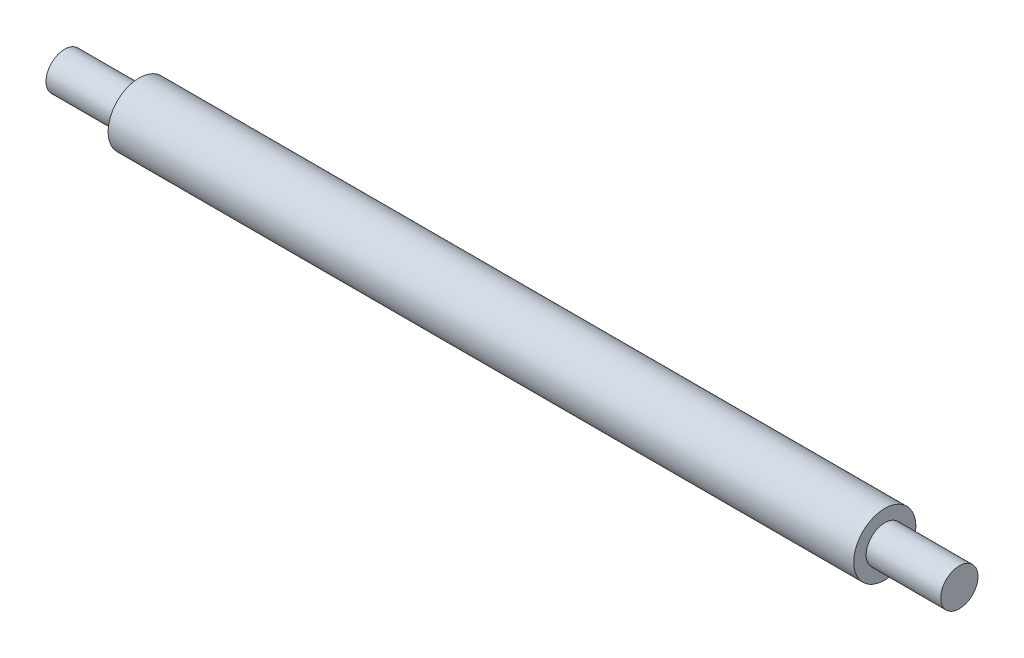
SolidWorks part; units mm, degrees
ref_plane "前视基准面" through (0, 0, 0) normal (0, 0, 1) x (1, 0, 0)
ref_plane "上视基准面" through (0, 0, 0) normal (0, 1, 0) x (1, 0, 0)
ref_plane "右视基准面" through (0, 0, 0) normal (1, 0, 0) x (0, 0, -1)
sketch "草图1" plane through (0, 0, 0) normal (1, 0, 0) x (0, 0, -1)
  circle A0 centre (0, 0) radius 2.5
  dimension "D1" = 5
extrude "凸台-拉伸1" add sketch "草图1" along normal blind 30 and the other way blind 30
sketch "草图2" plane through (30, 0, 0) normal (1, 0, 0) x (0, 0, -1)
  circle A0 centre (0, 0) radius 1.5
  dimension "D1" = 3
extrude "凸台-拉伸2" add sketch "草图2" along normal blind 6
sketch "草图3" plane through (-30, 0, 0) normal (-1, 0, 0) x (0, 0, 1)
  circle A0 centre (0, 0) radius 1.5
  dimension "D1" = 3
extrude "凸台-拉伸3" add sketch "草图3" along normal blind 6
